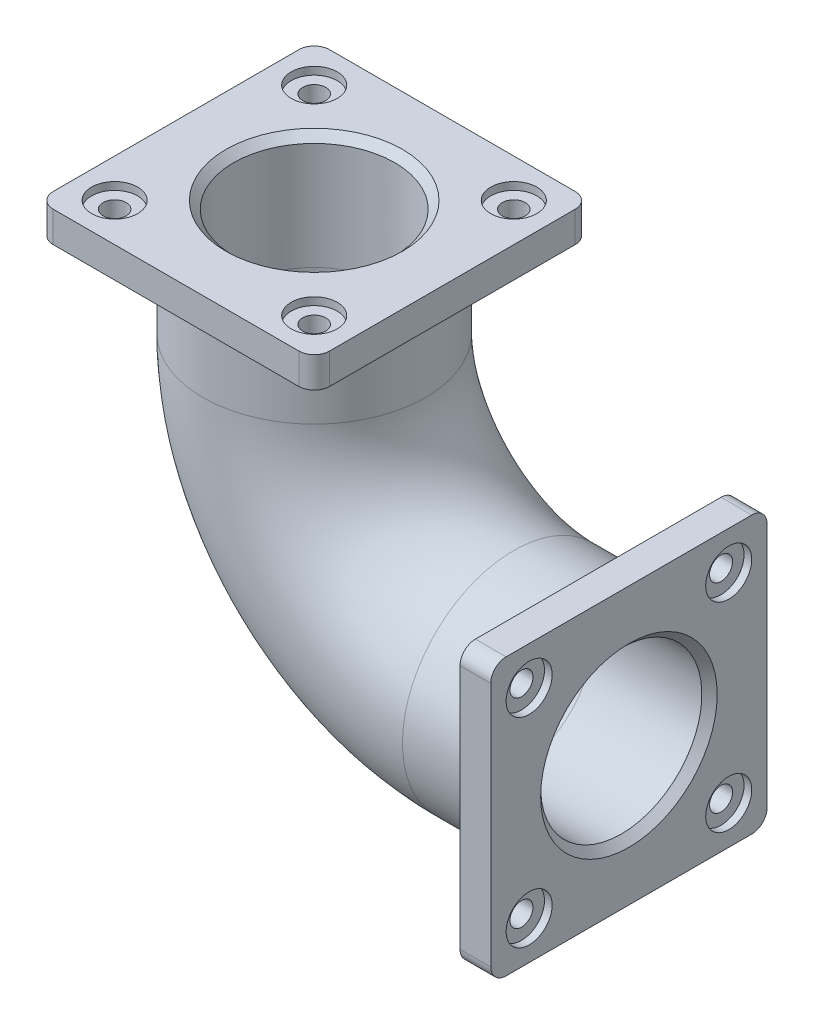
SolidWorks part; units mm, degrees
ref_plane "Front Plane" through (0, 0, 0) normal (0, 0, 1) x (1, 0, 0)
ref_plane "Top Plane" through (0, 0, 0) normal (0, 1, 0) x (1, 0, 0)
ref_plane "Right Plane" through (0, 0, 0) normal (1, 0, 0) x (0, 0, -1)
sketch "Sketch1" plane through (0, 0, 0) normal (0, 0, 1) x (1, 0, 0)
  line L0 (0, 0) -> (-150, 0)
  line L1 (-410, 260) -> (-410, 410)
  arc A0 (-150, 0) -> (-410, 260) centre (-150, 260) cw
  dimension "D2" = 260
  dimension "D1" = 150
sketch "Sketch2" plane through (0, 0, 0) normal (1, 0, 0) x (0, 0, -1)
  circle A0 centre (0, 0) radius 145
  dimension "D1" = 290
sweep "Sweep-Thin1" add profiles "Sketch2" path "Sketch1" parameters "D1"=40
sketch "Sketch3" plane through (0, 0, 0) normal (1, 0, 0) x (0, 0, -1)
  line L1 (-180, 180) -> (180, 180)
  line L2 (-180, 180) -> (-180, -180)
  line L3 (-180, -180) -> (180, -180)
  line L4 (180, 180) -> (180, -180)
  line L5 (-180, 180) -> (180, -180) construction
  line L6 (-180, -180) -> (180, 180) construction
  point P0 (0, 0)
  circle M4 centre (0, 0) radius 145
  dimension "D1" = 360
  dimension "D2" = 360
extrude "Boss-Extrude1" add sketch "Sketch3" against normal blind 40 contours L4 L1 L2 L3 M4 region at (0, 174.9088, 0)
sketch "Sketch4" plane through (0, 410, 0) normal (0, 1, 0) x (1, 0, 0)
  line L1 (-590, 180) -> (-230, 180)
  line L2 (-590, 180) -> (-590, -180)
  line L3 (-590, -180) -> (-230, -180)
  line L4 (-230, 180) -> (-230, -180)
  line L5 (-590, 180) -> (-230, -180) construction
  line L6 (-590, -180) -> (-230, 180) construction
  point P0 (-410, 0)
  circle M4 centre (-410, 0) radius 145
  dimension "D1" = 360
  dimension "D2" = 360
extrude "Boss-Extrude2" add sketch "Sketch4" against normal blind 40 contours L4 L1 L2 L3 M4 region at (-410, 410, -174.9088)
fillet "Fillet1" radius 20 8 edges at (-230, 390, -180) (-590, 390, -180) (-590, 390, 180) (-230, 390, 180) (-20, 180, -180) (-20, -180, 180) (-20, -180, -180) (-20, 180, 180)
chamfer "Chamfer1" distance 10 angle 45 2 edges at (0, 0, -105) (-305, 410, 0)
sketch "Sketch5" plane through (0, 0, 0) normal (1, 0, 0) x (0, 0, -1)
  line L1 (-130, 130) -> (130, 130) construction
  line L2 (-130, 130) -> (-130, -130) construction
  line L3 (-130, -130) -> (130, -130) construction
  line L4 (130, 130) -> (130, -130) construction
  line L5 (-130, 130) -> (130, -130) construction
  line L6 (-130, -130) -> (130, 130) construction
  circle A0 centre (-130, 130) radius 30
  point P0 (0, 0)
  dimension "D3" = 60
  dimension "D1" = 260
  dimension "D2" = 260
extrude "Cut-Extrude1" cut sketch "Sketch5" against normal blind 10
sketch "Sketch6" plane through (-10, 0, 0) normal (1, 0, 0) x (0, 0, -1)
  circle A0 centre (-130, 130) radius 15
  dimension "D1" = 30
extrude "Cut-Extrude2" cut sketch "Sketch6" against normal up to next
pattern_circular "CirPattern1" count 4 over 360 about axis through (-10, 0, 0) along (1, 0, 0) of "Cut-Extrude1", "Cut-Extrude2"
sketch "Sketch7" plane through (0, 410, 0) normal (0, 1, 0) x (1, 0, 0)
  line L1 (-540, 130) -> (-280, 130) construction
  line L2 (-540, 130) -> (-540, -130) construction
  line L3 (-540, -130) -> (-280, -130) construction
  line L4 (-280, 130) -> (-280, -130) construction
  line L5 (-540, 130) -> (-280, -130) construction
  line L6 (-540, -130) -> (-280, 130) construction
  circle A0 centre (-540, 130) radius 30
  point P0 (-410, 0)
  dimension "D3" = 60
  dimension "D1" = 260
  dimension "D2" = 260
extrude "Cut-Extrude3" cut sketch "Sketch7" against normal blind 10 contours A0
sketch "Sketch8" plane through (0, 400, 0) normal (0, 1, 0) x (1, 0, 0)
  circle A0 centre (-540, 130) radius 15
  dimension "D1" = 30
extrude "Cut-Extrude4" cut sketch "Sketch8" against normal up to next
pattern_circular "CirPattern2" count 4 over 360 about axis through (-410, 410, 0) along (0, -1, 0) of "Cut-Extrude3", "Cut-Extrude4"
